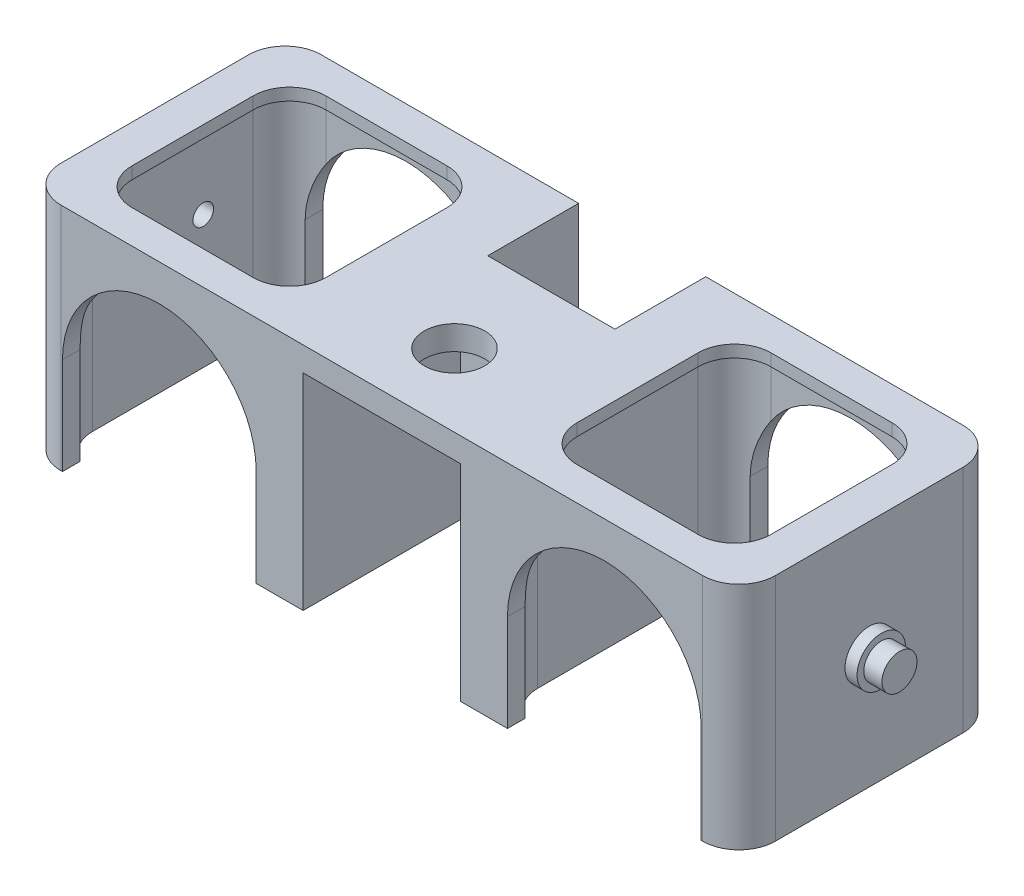
SolidWorks part; units mm, degrees
ref_plane "Front Plane" through (0, 0, 0) normal (0, 0, 1) x (1, 0, 0)
ref_plane "Top Plane" through (0, 0, 0) normal (0, 1, 0) x (1, 0, 0)
ref_plane "Right Plane" through (0, 0, 0) normal (1, 0, 0) x (0, 0, -1)
sketch "Sketch1" plane through (0, 0, 0) normal (0, 1, 0) x (1, 0, 0)
  line L1 (-59, -21.5) -> (59, -21.5)
  line L2 (-59, -21.5) -> (-59, 21.5)
  line L3 (-59, 21.5) -> (59, 21.5)
  line L4 (59, -21.5) -> (59, 21.5)
  line L5 (-59, -21.5) -> (59, 21.5) construction
  line L6 (-59, 21.5) -> (59, -21.5) construction
  point P0 (0, 0)
extrude "Boss-Extrude2" add sketch "Sketch1" along normal blind 38
sketch "Sketch2" plane through (0, 0, 0) normal (0, -1, 0) x (-1, 0, 0)
  line L0 (-59, 0) -> (-56, 0) construction
  line L1 (-59, -21.5) -> (-59, 21.5) construction
  line L2 (-17.5, -19.25) -> (-56, -19.25)
  line L3 (-17.5, -19.25) -> (-17.5, 19.25)
  line L4 (-56, -19.25) -> (-56, 19.25)
  line L5 (-17.5, 19.25) -> (-56, 19.25)
  line L6 (-17.5, -19.25) -> (-56, 19.25) construction
  line L7 (-56, -19.25) -> (-17.5, 19.25) construction
  line L8 (-56, 0) -> (-36.75, 0) construction
  line L11 (0, 21.5) -> (0, -21.5) construction
  line L12 (-59, 21.5) -> (59, 21.5) construction
  line L13 (59, -21.5) -> (-59, -21.5) construction
  line L14 (56, -19.25) -> (56, 19.25)
  line L15 (17.5, 19.25) -> (56, 19.25)
  line L16 (17.5, -19.25) -> (17.5, 19.25)
  line L17 (17.5, -19.25) -> (56, -19.25)
  point P6 (-36.75, 0)
extrude "Cut-Extrude1" cut sketch "Sketch2" against normal offset from surface (36 mm away) 2 up to face at (0, 38, 0)
sketch "Sketch3" plane through (0, 36, 0) normal (0, -1, 0) x (-1, 0, 0)
  line L0 (0, 0) -> (0, -15.6888) construction
  line L1 (-52.75, 16) -> (-20.75, 16)
  line L2 (-52.75, 16) -> (-52.75, -16)
  line L3 (-52.75, -16) -> (-20.75, -16)
  line L4 (-20.75, 16) -> (-20.75, -16)
  line L5 (-52.75, 16) -> (-20.75, -16) construction
  line L6 (-52.75, -16) -> (-20.75, 16) construction
  line L7 (52.75, 16) -> (52.75, -16)
  line L8 (52.75, -16) -> (20.75, -16)
  line L9 (20.75, 16) -> (20.75, -16)
  line L10 (52.75, 16) -> (20.75, 16)
  line L11 (-52.75, 0) -> (-59, 0) construction
  line L13 (-59, -21.5) -> (-59, 21.5) construction
  point P0 (-36.75, 0)
  point P16 (0, 0)
extrude "Cut-Extrude2" cut sketch "Sketch3" against normal up to surface (2 mm away) up to face at (0, 38, 0)
sketch "Sketch4" plane through (59, 0, 0) normal (1, 0, 0) x (0, 0, -1)
  line L0 (-21.5, 38) -> (21.5, 0) construction
  line L1 (0, 25.9282) -> (-6, 15.5359) construction
  line L2 (-6, 15.5359) -> (6, 15.5359) construction
  line L3 (6, 15.5359) -> (0, 25.9282) construction
  line L4 (-21.5, 0) -> (21.5, 38) construction
  circle A0 centre (0, 19) radius 3.4641 construction
  circle A4 centre (0, 19) radius 4
  point P15 (0, 19)
  dimension "D1" = 12
sketch "Sketch5" plane through (-59, 0, 0) normal (-1, 0, 0) x (0, 0, 1)
  line L0 (-21.5, 0) -> (21.5, 38) construction
  line L1 (-21.5, 38) -> (21.5, 0) construction
  line L3 (0, 13.2265) -> (5, 21.8868) construction
  line L4 (5, 21.8868) -> (-5, 21.8868) construction
  line L5 (-5, 21.8868) -> (0, 13.2265) construction
  circle A2 centre (0, 19) radius 2.8868 construction
  circle A3 centre (0, 13.2265) radius 1.7
  circle A4 centre (-5, 21.8868) radius 1.7
  circle A5 centre (5, 21.8868) radius 1.7
  point P8 (0, 19)
extrude "Cut-Extrude4" cut sketch "Sketch5" against normal up to surface (3 mm away) up to face at (-56, 18, 0)
sketch "Sketch14" plane through (0, 0, -21.5) normal (0, 0, -1) x (-1, 0, 0)
  line L0 (52.75, 0) -> (59, 0) construction
  line L8 (0, 0) -> (0, 38) construction
  line L14 (-59, 38) -> (59, 38) construction
  line L19 (-52.75, 0) -> (-20.75, 0)
  line L20 (52.75, 0) -> (20.75, 0)
  line L21 (52.75, 0) -> (52.75, 32)
  line L22 (52.75, 32) -> (20.75, 32)
  line L23 (20.75, 0) -> (20.75, 32)
  line L24 (-20.75, 0) -> (-20.75, 32)
  line L25 (-52.75, 32) -> (-20.75, 32)
  line L26 (-52.75, 0) -> (-52.75, 32)
extrude "Boss-Extrude3" add sketch "Sketch4" along normal blind 2
sketch "Sketch11" plane through (61, 0, 0) normal (1, 0, 0) x (0, 0, -1)
  circle A0 centre (0, 19) radius 2.9
extrude "Boss-Extrude4" add sketch "Sketch11" along normal blind 3
extrude "Cut-Extrude9" cut sketch "Sketch14" against normal up to surface (43 mm away) up to face at (0, 19, 21.5)
sketch "Sketch15" plane through (0, 38, 0) normal (0, 1, 0) x (1, 0, 0)
  line L0 (59, 21.5) -> (-59, 21.5) construction
  line L1 (10.5, 21.5) -> (-10.5, 21.5)
  line L2 (10.5, 21.5) -> (10.5, 6.5)
  line L3 (10.5, 6.5) -> (-10.5, 6.5)
  line L4 (-10.5, 21.5) -> (-10.5, 6.5)
  line L5 (0, 0) -> (0, 21.5) construction
  point P8 (0, 6.5)
extrude "Cut-Extrude10" cut sketch "Sketch15" against normal up to surface (38 mm away) contours L2 L1 L4 L3 up to face at (0, 0, 0)
fillet "Fillet2" radius 6 20 edges at (59, 19, -21.5) (-59, 19, -21.5) (-59, 19, 21.5) (59, 19, 21.5) (-17.5, 18, 19.25) (17.5, 18, 19.25) (-17.5, 18, -19.25) (17.5, 18, -19.25) (56, 18, 19.25) (56, 18, -19.25) (-56, 18, 19.25) (-56, 18, -19.25) (-52.75, 37, -16) (-52.75, 37, 16) (-20.75, 37, 16) (20.75, 37, -16) (20.75, 37, 16) (52.75, 37, 16) (52.75, 37, -16) (-20.75, 37, -16)
sketch "Sketch20" plane through (0, 0, 0) normal (0, -1, 0) x (1, 0, 0)
  line L0 (0, -6.5) -> (0, -18.5) construction
  line L1 (10.5, -6.5) -> (-10.5, -6.5) construction
  line L2 (-13.7, -18.5) -> (13.7, -18.5) construction
  circle A0 centre (13.7, -18.5) radius 1.5
  circle A1 centre (-13.7, -18.5) radius 1.5
  point P8 (0, -18.5)
extrude "Cut-Extrude15" cut sketch "Sketch20" against normal blind 26
sketch "Sketch18" plane through (0, 0, 0) normal (0, -1, 0) x (1, 0, 0)
  line L1 (-13, -4.5) -> (13, -4.5)
  line L2 (-13, -4.5) -> (-13, 21.5)
  line L3 (-13, 21.5) -> (13, 21.5)
  line L4 (13, -4.5) -> (13, 21.5)
  line L5 (-13, -4.5) -> (13, 21.5) construction
  line L6 (-13, 21.5) -> (13, -4.5) construction
  point P0 (0, 8.5)
  point P14 (0, 0)
extrude "Cut-Extrude13" cut sketch "Sketch18" against normal offset from surface (34 mm away) 4 contours L2 L1 L4 L3 up to face at (36.75, 38, 0)
sketch "Sketch19" plane through (0, 0, -4.5) normal (0, 0, 1) x (1, 0, 0)
  line L0 (-7, 18.2) -> (-7, 4) construction
  line L1 (-7, 11.1) -> (-13, 11.1) construction
  line L2 (-13, 34) -> (-13, 0) construction
  line L3 (-7, 4) -> (-7, 0) construction
  line L4 (-13, 0) -> (13, 0) construction
  line L5 (0, 0) -> (0, 34) construction
  line L6 (13, 34) -> (-13, 34) construction
  circle A0 centre (-7, 18.2) radius 1.5
  circle A1 centre (-7, 4) radius 1.5
  circle A2 centre (7, 18.2) radius 1.5
  circle A3 centre (7, 4) radius 1.5
extrude "Cut-Extrude14" cut sketch "Sketch19" against normal up to surface (2 mm away) up to face at (0, 19, -6.5)
sketch "Sketch21" plane through (0, 34, 0) normal (0, -1, 0) x (1, 0, 0)
  line L0 (13, -4.5) -> (-13, -4.5) construction
  line L1 (0, -4.5) -> (0, 9.5) construction
  circle A0 centre (0, 9.5) radius 5
extrude "Cut-Extrude16" cut sketch "Sketch21" against normal up to surface (4 mm away) up to face at (36.75, 38, 0)
fillet "Fillet3" radius 16 8 edges at (52.75, 32, -20.0413) (-20.75, 32, -20.0413) (-52.75, 32, -20.0413) (20.75, 32, -20.0413) (52.75, 32, 20.0413) (20.75, 32, 20.0413) (-20.75, 32, 20.0413) (-52.75, 32, 20.0413)
